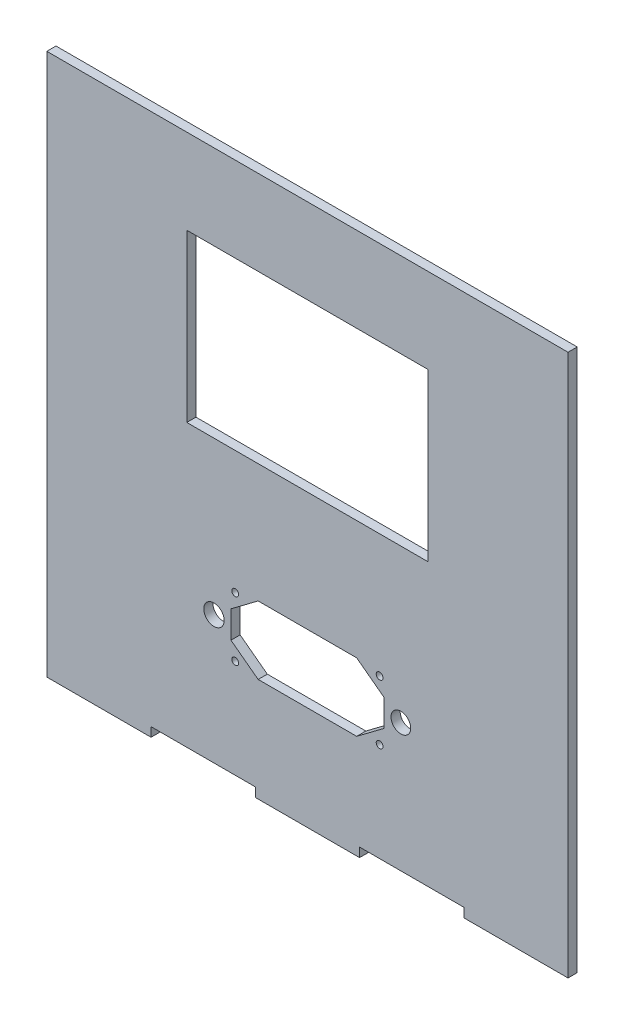
SolidWorks part; units mm, degrees
ref_plane "Ön Düzlem" through (0, 0, 0) normal (0, 0, 1) x (1, 0, 0)
ref_plane "Üst Düzlem" through (0, 0, 0) normal (0, 1, 0) x (1, 0, 0)
ref_plane "Sağ Düzlem" through (0, 0, 0) normal (1, 0, 0) x (0, 0, -1)
sketch "Sketch1" plane through (0, 0, 0) normal (0, 0, 1) x (1, 0, 0)
  line L21 (-46.02, -28) -> (-46.02, -25.3)
  line L22 (-15.34, -28) -> (-15.34, -25.3)
  line L23 (15.34, -28) -> (15.34, -25.3)
  line L24 (46.02, -28) -> (46.02, -25.3)
  line L26 (-76.7, -23) -> (-76.7, 13)
  line L27 (-76.7, -23) -> (-76.7, -25.3)
  line L28 (76.7, -23) -> (76.7, 13)
  line L30 (76.7, -25.3) -> (76.7, -23)
  line L33 (-46.02, -28) -> (-76.7, -28)
  line L34 (-76.7, -28) -> (-76.7, -25.3)
  line L35 (-15.34, -25.3) -> (-46.02, -25.3)
  line L36 (-15.34, -28) -> (15.34, -28)
  line L37 (15.34, -25.3) -> (46.02, -25.3)
  line L38 (46.02, -28) -> (76.7, -28)
  line L39 (76.7, -28) -> (76.7, -25.3)
  line L56 (-22.5, 16.5) -> (-14.5, 22.5)
  line L57 (-14.5, 22.5) -> (14.5, 22.5)
  line L58 (0, 2.5) -> (14.5, 2.5)
  line L59 (-14.5, 2.5) -> (-22.5, 8.5)
  line L60 (-22.5, 8.5) -> (-22.5, 16.5)
  line L61 (14.5, 2.5) -> (22.5, 8.5)
  line L62 (14.5, 22.5) -> (22.5, 16.5)
  line L63 (0, 2.5) -> (-14.5, 2.5)
  line L64 (22.5, 16.5) -> (22.5, 8.5)
  line L65 (35.5, 57.5) -> (-35.5, 57.5)
  line L66 (35.5, 57.5) -> (35.5, 106.5)
  line L67 (35.5, 106.5) -> (-35.5, 106.5)
  line L68 (-35.5, 57.5) -> (-35.5, 106.5)
  line L80 (76.7, 13) -> (76.7, 131.5)
  line L81 (-76.7, 131.5) -> (-76.7, 13)
  line L82 (76.7, 131.5) -> (-76.7, 131.5)
  circle A11 centre (-21.25, 3.75) radius 1
  circle A12 centre (-27.5, 12.5) radius 3
  circle A13 centre (-21.25, 21.25) radius 1
  circle A14 centre (21.25, 3.75) radius 1
  circle A15 centre (27.5, 12.5) radius 2.9
  circle A16 centre (21.25, 21.25) radius 1
  point P0 (0, 82)
extrude "Boss-Extrude3" add sketch "Sketch1" along normal blind 2.7
